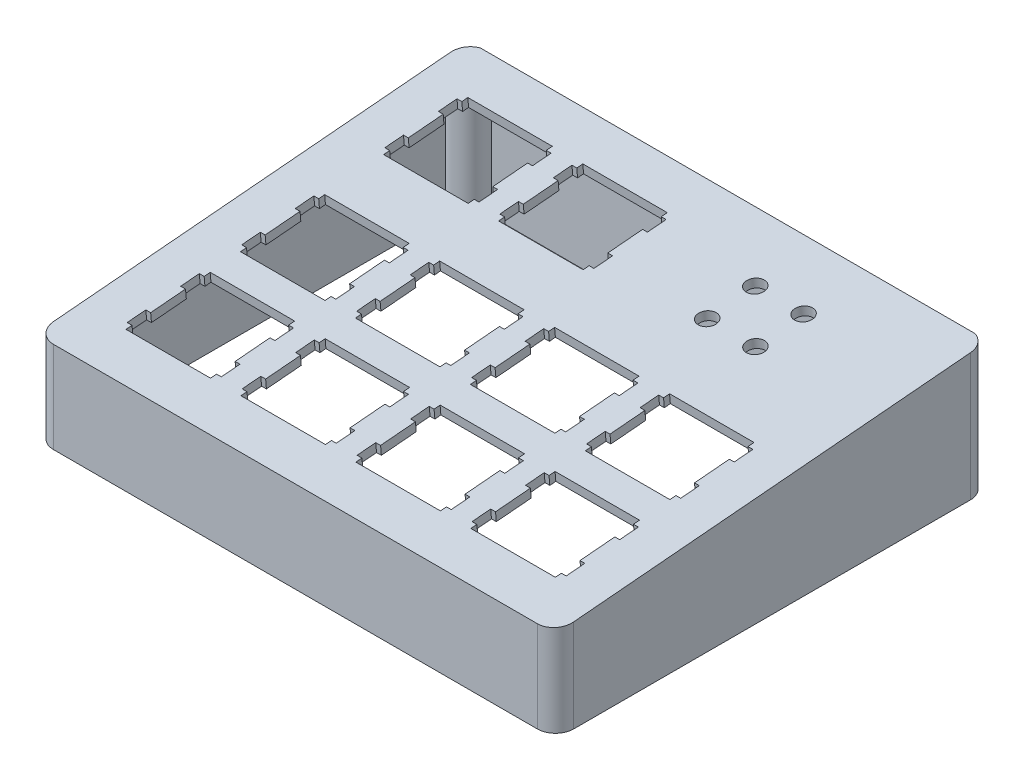
SolidWorks part; units mm, degrees
material "ABS"
ref_plane "Front" through (0, 0, 0) normal (0, 0, 1) x (1, 0, 0)
ref_plane "Top" through (0, 0, 0) normal (0, 1, 0) x (1, 0, 0)
ref_plane "Right" through (0, 0, 0) normal (1, 0, 0) x (0, 0, -1)
ref_axis "Axis1" through (80.9, 0, 0) along (-1, 0, 0)
ref_plane "Plane1" through (0, 0, 0) normal (0, 0.9962, 0.0872) x (1, 0, 0)
sketch "Sketch2" plane through (0, 0, 0) normal (0, 0.9962, 0.0872) x (1, 0, 0)
  line L1 (-43.1005, -35.9565) -> (43.1005, -35.9565)
  line L2 (-43.1005, -35.9565) -> (-43.1005, 35.9565)
  line L3 (-43.1005, 35.9565) -> (43.1005, 35.9565)
  line L4 (43.1005, -35.9565) -> (43.1005, 35.9565)
  line L5 (-43.1005, -35.9565) -> (43.1005, 35.9565) construction
  line L6 (-43.1005, 35.9565) -> (43.1005, -35.9565) construction
  point P0 (0, 0)
  dimension "D1" = 71.913
  dimension "D2" = 86.201
extrude "Boss-Extrude1" add sketch "Sketch2" along normal mid plane 1.5
sketch "Sketch7" plane through (0, 0.7471, 0.0654) normal (0, 0.9962, 0.0872) x (1, 0, 0)
  line L0 (16.5245, -2.3805) -> (21.5745, -2.3805) construction
  line L1 (19.0495, -2.3805) -> (19.0495, 21.432) construction
  line L2 (15.0495, 25.432) -> (23.0495, 25.432) construction
  line L3 (15.0495, 25.432) -> (15.0495, 17.432) construction
  line L4 (15.0495, 17.432) -> (23.0495, 17.432) construction
  line L5 (23.0495, 25.432) -> (23.0495, 17.432) construction
  line L6 (15.0495, 25.432) -> (23.0495, 17.432) construction
  line L7 (15.0495, 17.432) -> (23.0495, 25.432) construction
  line L8 (-43.1005, 35.9565) -> (-43.1005, -35.9565) construction
  line L9 (-43.1005, -35.9565) -> (43.1005, -35.9565) construction
  circle A0 centre (15.0495, 25.432) radius 1.5
  circle A1 centre (23.0495, 25.432) radius 1.5
  circle A2 centre (23.0495, 17.432) radius 1.5
  circle A3 centre (15.0495, 17.432) radius 1.5
  point P5 (-2.5255, 21.432)
  line B0 (43.1005, -35.9565) -> (-43.1005, -35.9565)
  line B1 (-43.1005, -35.9565) -> (-43.1005, 35.9565)
  line B2 (-43.1005, 35.9565) -> (43.1005, 35.9565)
  line B3 (43.1005, 35.9565) -> (43.1005, -35.9565)
  line B4 (21.5745, -14.4305) -> (21.5745, -15.4305)
  line B5 (21.5745, -15.4305) -> (20.7745, -15.4305)
  line B6 (20.7745, -15.4305) -> (20.7745, -18.5305)
  line B7 (20.7745, -18.5305) -> (21.5745, -18.5305)
  line B8 (21.5745, -18.5305) -> (21.5745, -24.3305)
  line B9 (21.5745, -24.3305) -> (20.7745, -24.3305)
  line B10 (20.7745, -24.3305) -> (20.7745, -27.4305)
  line B11 (20.7745, -27.4305) -> (21.5745, -27.4305)
  line B12 (21.5745, -27.4305) -> (21.5745, -28.4305)
  line B13 (21.5745, -28.4305) -> (35.5745, -28.4305)
  line B14 (35.5745, -28.4305) -> (35.5745, -27.4305)
  line B15 (35.5745, -27.4305) -> (36.3745, -27.4305)
  line B16 (36.3745, -27.4305) -> (36.3745, -24.3305)
  line B17 (36.3745, -24.3305) -> (35.5745, -24.3305)
  line B18 (35.5745, -24.3305) -> (35.5745, -18.5305)
  line B19 (35.5745, -18.5305) -> (36.3745, -18.5305)
  line B20 (36.3745, -18.5305) -> (36.3745, -15.4305)
  line B21 (36.3745, -15.4305) -> (35.5745, -15.4305)
  line B22 (35.5745, -15.4305) -> (35.5745, -14.4305)
  line B23 (35.5745, -14.4305) -> (21.5745, -14.4305)
  line B24 (2.5245, -14.4305) -> (2.5245, -15.4305)
  line B25 (2.5245, -15.4305) -> (1.7245, -15.4305)
  line B26 (1.7245, -15.4305) -> (1.7245, -18.5305)
  line B27 (1.7245, -18.5305) -> (2.5245, -18.5305)
  line B28 (2.5245, -18.5305) -> (2.5245, -24.3305)
  line B29 (2.5245, -24.3305) -> (1.7245, -24.3305)
  line B30 (1.7245, -24.3305) -> (1.7245, -27.4305)
  line B31 (1.7245, -27.4305) -> (2.5245, -27.4305)
  line B32 (2.5245, -27.4305) -> (2.5245, -28.4305)
  line B33 (2.5245, -28.4305) -> (16.5245, -28.4305)
  line B34 (16.5245, -28.4305) -> (16.5245, -27.4305)
  line B35 (16.5245, -27.4305) -> (17.3245, -27.4305)
  line B36 (17.3245, -27.4305) -> (17.3245, -24.3305)
  line B37 (17.3245, -24.3305) -> (16.5245, -24.3305)
  line B38 (16.5245, -24.3305) -> (16.5245, -18.5305)
  line B39 (16.5245, -18.5305) -> (17.3245, -18.5305)
  line B40 (17.3245, -18.5305) -> (17.3245, -15.4305)
  line B41 (17.3245, -15.4305) -> (16.5245, -15.4305)
  line B42 (16.5245, -15.4305) -> (16.5245, -14.4305)
  line B43 (16.5245, -14.4305) -> (2.5245, -14.4305)
  line B44 (-16.5255, -14.4305) -> (-16.5255, -15.4305)
  line B45 (-16.5255, -15.4305) -> (-17.3255, -15.4305)
  line B46 (-17.3255, -15.4305) -> (-17.3255, -18.5305)
  line B47 (-17.3255, -18.5305) -> (-16.5255, -18.5305)
  line B48 (-16.5255, -18.5305) -> (-16.5255, -24.3305)
  line B49 (-16.5255, -24.3305) -> (-17.3255, -24.3305)
  line B50 (-17.3255, -24.3305) -> (-17.3255, -27.4305)
  line B51 (-17.3255, -27.4305) -> (-16.5255, -27.4305)
  line B52 (-16.5255, -27.4305) -> (-16.5255, -28.4305)
  line B53 (-16.5255, -28.4305) -> (-2.5255, -28.4305)
  line B54 (-2.5255, -28.4305) -> (-2.5255, -27.4305)
  line B55 (-2.5255, -27.4305) -> (-1.7255, -27.4305)
  line B56 (-1.7255, -27.4305) -> (-1.7255, -24.3305)
  line B57 (-1.7255, -24.3305) -> (-2.5255, -24.3305)
  line B58 (-2.5255, -24.3305) -> (-2.5255, -18.5305)
  line B59 (-2.5255, -18.5305) -> (-1.7255, -18.5305)
  line B60 (-1.7255, -18.5305) -> (-1.7255, -15.4305)
  line B61 (-1.7255, -15.4305) -> (-2.5255, -15.4305)
  line B62 (-2.5255, -15.4305) -> (-2.5255, -14.4305)
  line B63 (-2.5255, -14.4305) -> (-16.5255, -14.4305)
  line B64 (-35.5765, -14.4305) -> (-35.5765, -15.4305)
  line B65 (-35.5765, -15.4305) -> (-36.3765, -15.4305)
  line B66 (-36.3765, -15.4305) -> (-36.3765, -18.5305)
  line B67 (-36.3765, -18.5305) -> (-35.5765, -18.5305)
  line B68 (-35.5765, -18.5305) -> (-35.5765, -24.3305)
  line B69 (-35.5765, -24.3305) -> (-36.3765, -24.3305)
  line B70 (-36.3765, -24.3305) -> (-36.3765, -27.4305)
  line B71 (-36.3765, -27.4305) -> (-35.5765, -27.4305)
  line B72 (-35.5765, -27.4305) -> (-35.5765, -28.4305)
  line B73 (-35.5765, -28.4305) -> (-21.5755, -28.4305)
  line B74 (-21.5755, -28.4305) -> (-21.5755, -27.4305)
  line B75 (-21.5755, -27.4305) -> (-20.7755, -27.4305)
  line B76 (-20.7755, -27.4305) -> (-20.7755, -24.3305)
  line B77 (-20.7755, -24.3305) -> (-21.5755, -24.3305)
  line B78 (-21.5755, -24.3305) -> (-21.5755, -18.5305)
  line B79 (-21.5755, -18.5305) -> (-20.7755, -18.5305)
  line B80 (-20.7755, -18.5305) -> (-20.7755, -15.4305)
  line B81 (-20.7755, -15.4305) -> (-21.5755, -15.4305)
  line B82 (-21.5755, -15.4305) -> (-21.5755, -14.4305)
  line B83 (-21.5755, -14.4305) -> (-35.5765, -14.4305)
  line B84 (21.5745, 4.6195) -> (21.5745, 3.6195)
  line B85 (21.5745, 3.6195) -> (20.7745, 3.6195)
  line B86 (20.7745, 3.6195) -> (20.7745, 0.5195)
  line B87 (20.7745, 0.5195) -> (21.5745, 0.5195)
  line B88 (21.5745, 0.5195) -> (21.5745, -5.2805)
  line B89 (21.5745, -5.2805) -> (20.7745, -5.2805)
  line B90 (20.7745, -5.2805) -> (20.7745, -8.3805)
  line B91 (20.7745, -8.3805) -> (21.5745, -8.3805)
  line B92 (21.5745, -8.3805) -> (21.5745, -9.3805)
  line B93 (21.5745, -9.3805) -> (35.5745, -9.3805)
  line B94 (35.5745, -9.3805) -> (35.5745, -8.3805)
  line B95 (35.5745, -8.3805) -> (36.3745, -8.3805)
  line B96 (36.3745, -8.3805) -> (36.3745, -5.2805)
  line B97 (36.3745, -5.2805) -> (35.5745, -5.2805)
  line B98 (35.5745, -5.2805) -> (35.5745, 0.5195)
  line B99 (35.5745, 0.5195) -> (36.3745, 0.5195)
  line B100 (36.3745, 0.5195) -> (36.3745, 3.6195)
  line B101 (36.3745, 3.6195) -> (35.5745, 3.6195)
  line B102 (35.5745, 3.6195) -> (35.5745, 4.6195)
  line B103 (35.5745, 4.6195) -> (21.5745, 4.6195)
  line B104 (2.5245, 4.6195) -> (2.5245, 3.6195)
  line B105 (2.5245, 3.6195) -> (1.7245, 3.6195)
  line B106 (1.7245, 3.6195) -> (1.7245, 0.5195)
  line B107 (1.7245, 0.5195) -> (2.5245, 0.5195)
  line B108 (2.5245, 0.5195) -> (2.5245, -5.2805)
  line B109 (2.5245, -5.2805) -> (1.7245, -5.2805)
  line B110 (1.7245, -5.2805) -> (1.7245, -8.3805)
  line B111 (1.7245, -8.3805) -> (2.5245, -8.3805)
  line B112 (2.5245, -8.3805) -> (2.5245, -9.3805)
  line B113 (2.5245, -9.3805) -> (16.5245, -9.3805)
  line B114 (16.5245, -9.3805) -> (16.5245, -8.3805)
  line B115 (16.5245, -8.3805) -> (17.3245, -8.3805)
  line B116 (17.3245, -8.3805) -> (17.3245, -5.2805)
  line B117 (17.3245, -5.2805) -> (16.5245, -5.2805)
  line B118 (16.5245, -5.2805) -> (16.5245, 0.5195)
  line B119 (16.5245, 0.5195) -> (17.3245, 0.5195)
  line B120 (17.3245, 0.5195) -> (17.3245, 3.6195)
  line B121 (17.3245, 3.6195) -> (16.5245, 3.6195)
  line B122 (16.5245, 3.6195) -> (16.5245, 4.6195)
  line B123 (16.5245, 4.6195) -> (2.5245, 4.6195)
  line B124 (-16.5255, 4.6195) -> (-16.5255, 3.6195)
  line B125 (-16.5255, 3.6195) -> (-17.3255, 3.6195)
  line B126 (-17.3255, 3.6195) -> (-17.3255, 0.5195)
  line B127 (-17.3255, 0.5195) -> (-16.5255, 0.5195)
  line B128 (-16.5255, 0.5195) -> (-16.5255, -5.2805)
  line B129 (-16.5255, -5.2805) -> (-17.3255, -5.2805)
  line B130 (-17.3255, -5.2805) -> (-17.3255, -8.3805)
  line B131 (-17.3255, -8.3805) -> (-16.5255, -8.3805)
  line B132 (-16.5255, -8.3805) -> (-16.5255, -9.3805)
  line B133 (-16.5255, -9.3805) -> (-2.5255, -9.3805)
  line B134 (-2.5255, -9.3805) -> (-2.5255, -8.3805)
  line B135 (-2.5255, -8.3805) -> (-1.7255, -8.3805)
  line B136 (-1.7255, -8.3805) -> (-1.7255, -5.2805)
  line B137 (-1.7255, -5.2805) -> (-2.5255, -5.2805)
  line B138 (-2.5255, -5.2805) -> (-2.5255, 0.5195)
  line B139 (-2.5255, 0.5195) -> (-1.7255, 0.5195)
  line B140 (-1.7255, 0.5195) -> (-1.7255, 3.6195)
  line B141 (-1.7255, 3.6195) -> (-2.5255, 3.6195)
  line B142 (-2.5255, 3.6195) -> (-2.5255, 4.6195)
  line B143 (-2.5255, 4.6195) -> (-16.5255, 4.6195)
  line B144 (-35.5765, 4.6195) -> (-35.5765, 3.6195)
  line B145 (-35.5765, 3.6195) -> (-36.3765, 3.6195)
  line B146 (-36.3765, 3.6195) -> (-36.3765, 0.5195)
  line B147 (-36.3765, 0.5195) -> (-35.5765, 0.5195)
  line B148 (-35.5765, 0.5195) -> (-35.5765, -5.2805)
  line B149 (-35.5765, -5.2805) -> (-36.3765, -5.2805)
  line B150 (-36.3765, -5.2805) -> (-36.3765, -8.3805)
  line B151 (-36.3765, -8.3805) -> (-35.5765, -8.3805)
  line B152 (-35.5765, -8.3805) -> (-35.5765, -9.3805)
  line B153 (-35.5765, -9.3805) -> (-21.5755, -9.3805)
  line B154 (-21.5755, -9.3805) -> (-21.5755, -8.3805)
  line B155 (-21.5755, -8.3805) -> (-20.7755, -8.3805)
  line B156 (-20.7755, -8.3805) -> (-20.7755, -5.2805)
  line B157 (-20.7755, -5.2805) -> (-21.5755, -5.2805)
  line B158 (-21.5755, -5.2805) -> (-21.5755, 0.5195)
  line B159 (-21.5755, 0.5195) -> (-20.7755, 0.5195)
  line B160 (-20.7755, 0.5195) -> (-20.7755, 3.6195)
  line B161 (-20.7755, 3.6195) -> (-21.5755, 3.6195)
  line B162 (-21.5755, 3.6195) -> (-21.5755, 4.6195)
  line B163 (-21.5755, 4.6195) -> (-35.5765, 4.6195)
  line B164 (-16.5255, 28.4325) -> (-16.5255, 27.4325)
  line B165 (-16.5255, 27.4325) -> (-17.3255, 27.4325)
  line B166 (-17.3255, 27.4325) -> (-17.3255, 24.3315)
  line B167 (-17.3255, 24.3315) -> (-16.5255, 24.3315)
  line B168 (-16.5255, 24.3315) -> (-16.5255, 18.5325)
  line B169 (-16.5255, 18.5325) -> (-17.3255, 18.5325)
  line B170 (-17.3255, 18.5325) -> (-17.3255, 15.4315)
  line B171 (-17.3255, 15.4315) -> (-16.5255, 15.4315)
  line B172 (-16.5255, 15.4315) -> (-16.5255, 14.4315)
  line B173 (-16.5255, 14.4315) -> (-2.5255, 14.4315)
  line B174 (-2.5255, 14.4315) -> (-2.5255, 15.4315)
  line B175 (-2.5255, 15.4315) -> (-1.7255, 15.4315)
  line B176 (-1.7255, 15.4315) -> (-1.7255, 18.5325)
  line B177 (-1.7255, 18.5325) -> (-2.5255, 18.5325)
  line B178 (-2.5255, 18.5325) -> (-2.5255, 24.3315)
  line B179 (-2.5255, 24.3315) -> (-1.7255, 24.3315)
  line B180 (-1.7255, 24.3315) -> (-1.7255, 27.4325)
  line B181 (-1.7255, 27.4325) -> (-2.5255, 27.4325)
  line B182 (-2.5255, 27.4325) -> (-2.5255, 28.4325)
  line B183 (-2.5255, 28.4325) -> (-16.5255, 28.4325)
  line B184 (-35.5765, 28.4325) -> (-35.5765, 27.4325)
  line B185 (-35.5765, 27.4325) -> (-36.3765, 27.4325)
  line B186 (-36.3765, 27.4325) -> (-36.3765, 24.3315)
  line B187 (-36.3765, 24.3315) -> (-35.5765, 24.3315)
  line B188 (-35.5765, 24.3315) -> (-35.5765, 18.5325)
  line B189 (-35.5765, 18.5325) -> (-36.3765, 18.5325)
  line B190 (-36.3765, 18.5325) -> (-36.3765, 15.4315)
  line B191 (-36.3765, 15.4315) -> (-35.5765, 15.4315)
  line B192 (-35.5765, 15.4315) -> (-35.5765, 14.4315)
  line B193 (-35.5765, 14.4315) -> (-21.5755, 14.4315)
  line B194 (-21.5755, 14.4315) -> (-21.5755, 15.4315)
  line B195 (-21.5755, 15.4315) -> (-20.7755, 15.4315)
  line B196 (-20.7755, 15.4315) -> (-20.7755, 18.5325)
  line B197 (-20.7755, 18.5325) -> (-21.5755, 18.5325)
  line B198 (-21.5755, 18.5325) -> (-21.5755, 24.3315)
  line B199 (-21.5755, 24.3315) -> (-20.7755, 24.3315)
  line B200 (-20.7755, 24.3315) -> (-20.7755, 27.4325)
  line B201 (-20.7755, 27.4325) -> (-21.5755, 27.4325)
  line B202 (-21.5755, 27.4325) -> (-21.5755, 28.4325)
  line B203 (-21.5755, 28.4325) -> (-35.5765, 28.4325)
  dimension "D1" = 3
  dimension "D2" = 8
sketch_block_instance "Block1-1"
sketch_block "Block1"
extrude "Cut-Extrude1" cut sketch "Sketch7" against normal up to next contours B42 B43 B24 B25 B26 B27 B28 B29 B30 B31 B32 B33 B34 B35 B36 B37 B38 B39 B40 B41 | B22 B23 B4 B5 B6 B7 B8 B9 B10 B11 B12 B13 B14 B15 B16 B17 B18 B19 B20 B21 | B122 B123 B104 B105 B106 B107 B108 B109 B110 B111 B112 B113 B114 B115 B116 B117 B118 B119 B120 B121 | B62 B63 B44 B45 B46 B47 B48 B49 B50 B51 B52 B53 B54 B55 B56 B57 B58 B59 B60 B61 | B142 B143 B124 B125 B126 B127 B128 B129 B130 B131 B132 B133 B134 B135 B136 B137 B138 B139 B140 B141 | B82 B83 B64 B65 B66 B67 B68 B69 B70 B71 B72 B73 B74 B75 B76 B77 B78 B79 B80 B81 | B162 B163 B144 B145 B146 B147 B148 B149 B150 B151 B152 B153 B154 B155 B156 B157 B158 B159 B160 B161 | B102 B103 B84 B85 B86 B87 B88 B89 B90 B91 B92 B93 B94 B95 B96 B97 B98 B99 B100 B101 | B202 B203 B184 B185 B186 B187 B188 B189 B190 B191 B192 B193 B194 B195 B196 B197 B198 B199 B200 B201 | B182 B183 B164 B165 B166 B167 B168 B169 B170 B171 B172 B173 B174 B175 B176 B177 B178 B179 B180 B181 | A3 | A0 | A1 | A2 region at (15.0495, 2.9637, -25.2699) region at (23.0495, 2.9637, -25.2699) region at (23.0495, 2.2664, -17.3003) region at (15.0495, 2.2664, -17.3003) region at (28.5745, -1.1206, 21.4143) region at (9.5245, -1.1206, 21.4143) region at (-9.5255, -1.1206, 21.4143) region at (-28.576, -1.1206, 21.4143) region at (28.5745, 0.5397, 2.4368) region at (9.5245, 0.5397, 2.4368) region at (-9.5255, 0.5397, 2.4368) region at (-28.576, 0.5397, 2.4368) region at (-9.5255, 2.6151, -21.2851) region at (-28.576, 2.6151, -21.2851)
ref_plane "Plane2" through (0, -17.5, 0) normal (0, -1, 0) x (-1, 0, 0)
sketch "Sketch3" plane through (0, -17.5, 0) normal (0, -1, 0) x (-1, 0, 0)
  line L5 (-43.1005, 35.885) -> (43.1005, 35.885)
  line L6 (-43.1005, 35.885) -> (-43.1005, -35.885)
  line L7 (-43.1005, -35.885) -> (43.1005, -35.885)
  line L8 (43.1005, 35.885) -> (43.1005, -35.885)
extrude "Extrude-Thin1" add sketch "Sketch3" against normal up to next thin thin type one direction reverse wall 2
fillet "Fillet1" radius 3 4 edges at (43.1005, -7.5567, -35.885) (-43.1005, -7.5567, -35.885) (43.1005, -9.9433, 35.885) (-43.1005, -9.9433, 35.885)
sketch "Sketch4" plane through (0, -17.5, 0) normal (0, -1, 0) x (1, 0, 0)
  circle A1 centre (-40.1005, 32.885) radius 3
  arc A2 (-40.1005, 35.885) -> (-43.1005, 32.885) centre (-40.1005, 32.885) ccw construction
  circle A3 centre (40.1005, 32.885) radius 3
  circle A4 centre (40.1005, -32.885) radius 3
  circle A5 centre (-40.1005, -32.885) radius 3
  arc A6 (43.1005, 32.885) -> (40.1005, 35.885) centre (40.1005, 32.885) ccw construction
extrude "Boss-Extrude2" add sketch "Sketch4" against normal up to next
hole_wizard "Tap Drill for #2-56 Tap1" positions "Sketch5" profile "Sketch6" hole size "#2-56" standard "ANSI Inch"
sketch "Sketch5" plane through (0, -17.5, 0) normal (0, -1, 0) x (-1, 0, 0)
  point P0 (40.1005, -32.885)
  point P3 (-40.1005, -32.885)
  point P6 (-40.1005, 32.885)
  point P9 (40.1005, 32.885)
sketch "Sketch6" plane through (-40.1005, -17.5, 32.885) normal (1, 0, 0) x (0, 0, -1)
  line L0 (0, 0) -> (0, 13.2342)
  line L1 (0, 13.2342) -> (0.889, 12.7)
  line L2 (0.889, 12.7) -> (0.889, 0)
  line L5 (0.889, 0) -> (0, 0)
  line L10 (0, 13.2342) -> (-0.889, 12.7) construction
  line L11 (0, -6.35) -> (0, 107.95) construction
  dimension "Hole Dia." = 1.778
  dimension "Hole Depth" = 12.7
  dimension "Drill Angle" = 118
